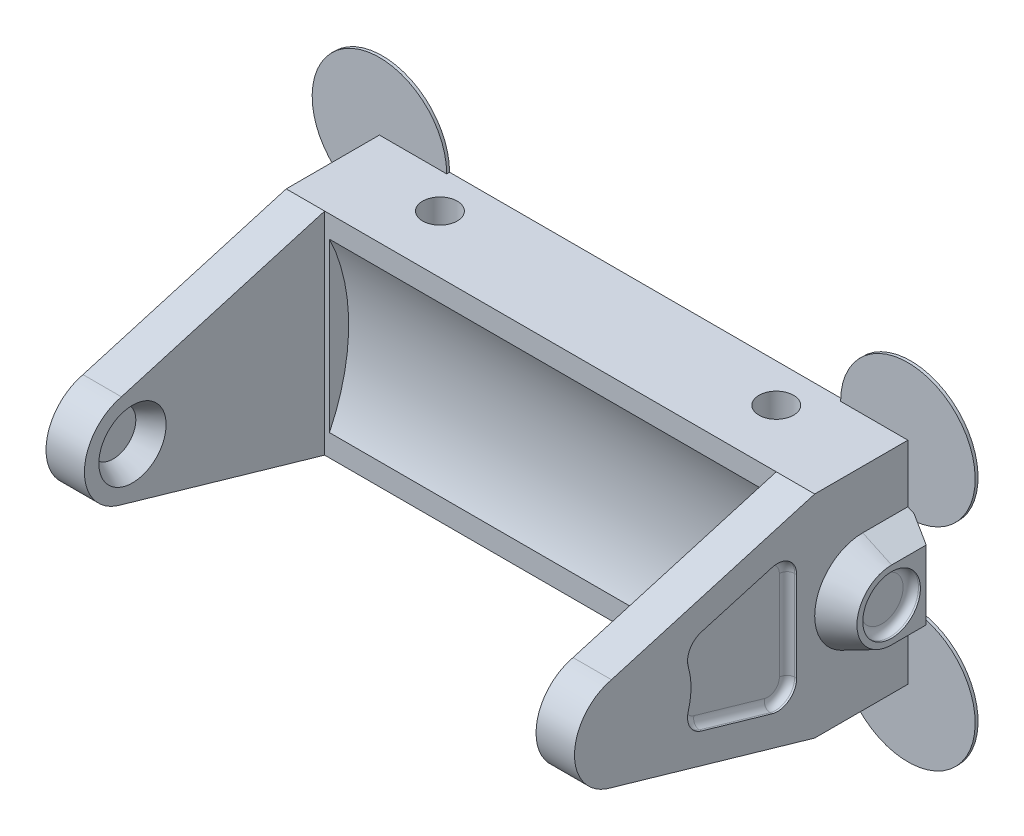
SolidWorks part; units mm, degrees
material "Oak"
ref_plane "Front Plane" through (0, 0, 0) normal (0, 0, 1) x (1, 0, 0)
ref_plane "Top Plane" through (0, 0, 0) normal (0, 1, 0) x (1, 0, 0)
ref_plane "Right Plane" through (0, 0, 0) normal (1, 0, 0) x (0, 0, -1)
sketch "Sketch1" plane through (0, 0, 0) normal (0, 0, 1) x (1, 0, 0)
  line L1 (-27.5, 11) -> (27.5, 11)
  line L2 (-27.5, 11) -> (-27.5, -11)
  line L3 (-27.5, -11) -> (27.5, -11)
  line L4 (27.5, 11) -> (27.5, -11)
  line L5 (-27.5, 11) -> (27.5, -11) construction
  line L6 (-27.5, -11) -> (27.5, 11) construction
  point P0 (0, 0)
  dimension "D1" = 22
  dimension "D2" = 55
extrude "Boss-Extrude1" add sketch "Sketch1" along normal blind 10
sketch "Sketch2" plane through (0, 0, 0) normal (0, 1, 0) x (1, 0, 0)
  line L0 (-17.5, -4) -> (17.5, -4) construction
  circle A0 centre (-17.5, -4) radius 1.8
  circle A1 centre (17.5, -4) radius 1.8
  point P4 (0, -4)
  dimension "D1" = 3.6
  dimension "D2" = 4
  dimension "D3" = 35
extrude "Cut-Extrude1" cut sketch "Sketch2" against normal through all both and the other way through all
sketch "Sketch3" plane through (0, 0, 0) normal (1, 0, 0) x (0, 0, -1)
  line L0 (-31.1511, 4.8351) -> (-10, 11)
  line L1 (-31.1677, -4.8923) -> (-10, -11)
  line L2 (-10, -11) -> (-10, 11)
  arc A0 (-31.1677, -4.8923) -> (-31.1511, 4.8351) centre (-30, -0.0306) cw
  dimension "D2" = 5
  dimension "D1" = 30
extrude "Boss-Extrude2" add sketch "Sketch3" along normal blind 4 from vertex starting at point (-27.5, 11, 10)
extrude "Boss-Extrude3" add sketch "Sketch3<2>" against normal blind 4 from vertex starting at point (27.5, 11, 10)
sketch "Sketch3<2>" plane through (0, 0, 0) normal (1, 0, 0) x (0, 0, -1) same geometry as "Sketch3"
sketch "Sketch4" plane through (0, 0, 0) normal (1, 0, 0) x (0, 0, -1)
  circle A0 centre (-30, 0) radius 3.5
  dimension "D1" = 7
  dimension "D2" = 30
extrude "Cut-Extrude2" cut sketch "Sketch4" against normal blind 2 draft 30 from surface starting at face at (-23.5, -0.0127, 21.5399)
extrude "Cut-Extrude3" cut sketch "Sketch4<2>" along normal blind 2 draft 30 from surface starting at face at (23.5, -0.0127, 21.5399)
sketch "Sketch4<2>" plane through (0, 0, 0) normal (1, 0, 0) x (0, 0, -1) same geometry as "Sketch4"
sketch "Sketch5" plane through (0, 0, 0) normal (1, 0, 0) x (0, 0, -1)
  line L0 (-20.6143, 18.5863) -> (-20.0581, -18.3555)
  arc A0 (-20.6143, 18.5863) -> (-20.0581, -18.3555) centre (-28, 0) cw
  dimension "D2" = 20
  dimension "D1" = 28
extrude "Cut-Extrude4" cut sketch "Sketch5" against normal mid plane 46
sketch "Sketch6" plane through (0, 0, 0) normal (1, 0, 0) x (0, 0, -1)
  line L0 (-5, -5) -> (0, -5)
  line L1 (0, -5) -> (0, 5)
  line L2 (0, 5) -> (-5, 5)
  circle A0 centre (-5, 0) radius 5
  dimension "D1" = 10
  dimension "D2" = 5
extrude "Boss-Extrude4" add sketch "Sketch6" along normal blind 3 draft 25 from surface contours A0 L1 L2 | A0 L0 L1 | A0 region at (0, -3.8832, 1.1168) region at (0, 0, 5) region at (0, 3.8832, 1.1168) starting at face at (27.5, -0.0085, 14.3599)
extrude "Boss-Extrude5" add sketch "Sketch6<2>" against normal blind 3 draft 25 from surface contours A0 L1 L2 | A0 L0 L1 | A0 region at (0, -3.8832, 1.1168) region at (0, 0, 5) region at (0, 3.8832, 1.1168) starting at face at (-27.5, -0.0085, 14.3599)
sketch "Sketch6<2>" plane through (0, 0, 0) normal (1, 0, 0) x (0, 0, -1) same geometry as "Sketch6"
sketch "Sketch7" plane through (0, 0, 0) normal (1, 0, 0) x (0, 0, -1)
  circle A0 centre (-5, 0) radius 3
  dimension "D1" = 6
extrude "Cut-Extrude5" cut sketch "Sketch7" against normal blind 1 from surface starting at face at (30.5, 0, 4.0997)
extrude "Cut-Extrude6" cut sketch "Sketch7<2>" along normal blind 1 from surface starting at face at (-30.5, 0, 4.0997)
sketch "Sketch7<2>" plane through (0, 0, 0) normal (1, 0, 0) x (0, 0, -1) same geometry as "Sketch7"
sketch "Sketch8" plane through (0, 0, 0) normal (1, 0, 0) x (0, 0, -1)
  line L0 (-11.8784, 4.6728) -> (-11.8784, -4.6728)
  line L1 (-14.4341, -6.5941) -> (-21.7894, -4.4664)
  line L2 (-21.7894, 4.4664) -> (-14.4341, 6.5941)
  arc A0 (-23.1543, -1.9876) -> (-23.1543, 1.9876) centre (-30, 0) ccw
  arc A1 (-11.8784, -4.6728) -> (-14.4341, -6.5941) centre (-13.8784, -4.6728) cw
  arc A2 (-11.8784, 4.6728) -> (-14.4341, 6.5941) centre (-13.8784, 4.6728) ccw
  arc A3 (-23.1543, -1.9876) -> (-21.7894, -4.4664) centre (-21.2336, -2.5452) ccw
  arc A4 (-23.1543, 1.9876) -> (-21.7894, 4.4664) centre (-21.2336, 2.5452) cw
  point P6 (-11.8784, 0)
  point P7 (-22.8716, 0)
  dimension "D1" = 2
extrude "Cut-Extrude7" cut sketch "Sketch8" against normal blind 1 from surface starting at face at (27.5, -0.0051, 10.1159)
extrude "Cut-Extrude8" cut sketch "Sketch8<2>" along normal blind 1 from surface starting at face at (-27.5, -0.0051, 10.1159)
sketch "Sketch8<2>" plane through (0, 0, 0) normal (1, 0, 0) x (0, 0, -1) same geometry as "Sketch8"
sketch "Sketch9" plane through (0, 0, 0) normal (0, 0, 1) x (1, 0, 0)
  circle A0 centre (27.5, 11) radius 7.0012
  circle A1 centre (-27.5, 11) radius 7.0012
  circle A2 centre (-27.5, -11) radius 7.0012
  circle A3 centre (27.5, -11) radius 7.0012
extrude "Boss-Extrude6" add sketch "Sketch9" along normal blind 0.3
fillet "Fillet1" radius 0.8 18 edges at (26.5, 0, 22.8716) (26.5, 3.5099, 22.9856) (26.5, 5.5302, 18.1117) (26.5, 6.2715, 12.6766) (26.5, 0, 11.8784) (26.5, -6.2715, 12.6766) (26.5, -5.5302, 18.1117) (26.5, -3.5099, 22.9856) (-26.5, -3.5099, 22.9856) (-26.5, -5.5302, 18.1117) (-26.5, -6.2715, 12.6766) (-26.5, 0, 11.8784) (-26.5, 6.2715, 12.6766) (-26.5, 5.5302, 18.1117) (-26.5, 3.5099, 22.9856) (-26.5, 0, 22.8716) (-29.5, 3, 5) (29.5, -3, 5)
